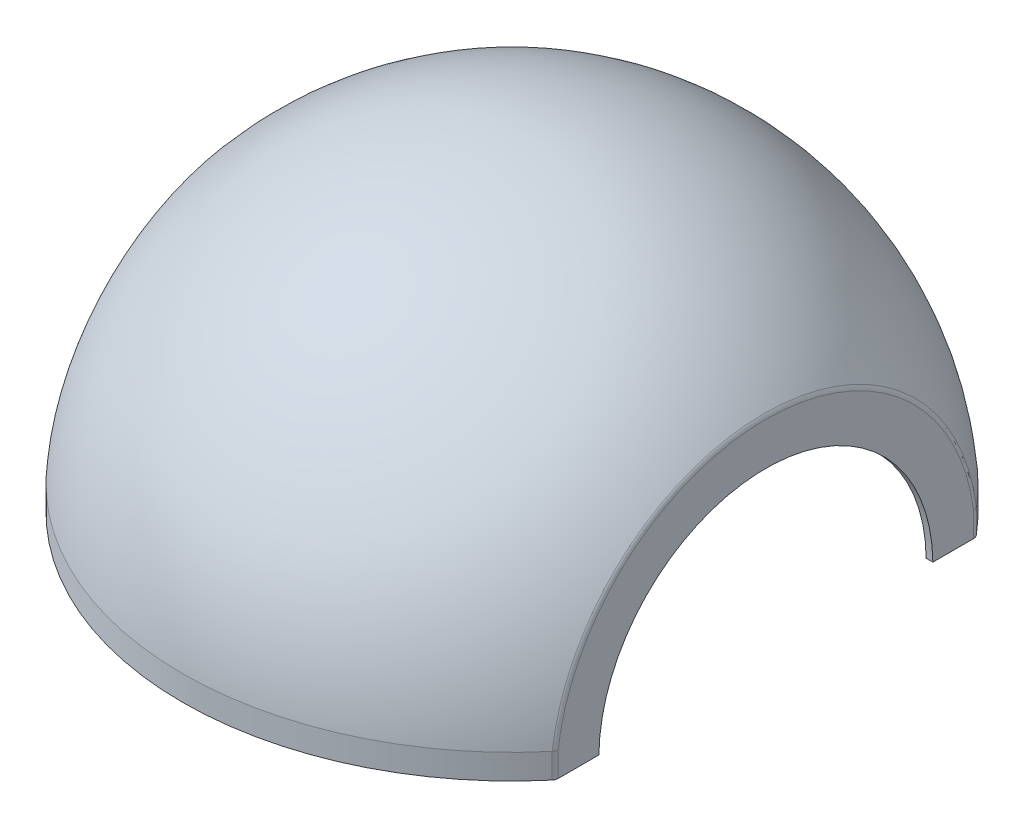
SolidWorks part; units mm, degrees
ref_plane "Face" through (0, 0, 0) normal (0, 0, 1) x (1, 0, 0)
ref_plane "Dessus" through (0, 0, 0) normal (0, 1, 0) x (1, 0, 0)
ref_plane "Droite" through (0, 0, 0) normal (1, 0, 0) x (0, 0, -1)
sketch "Esquisse1" plane through (0, 0, 0) normal (0, 0, 1) x (1, 0, 0)
  line L1 (148, 12.1758) -> (148, 1)
  line L3 (145, 1) -> (145, 12.052)
  line L5 (145, 1) -> (148, 1)
  line L6 (0, 0) -> (0, 184.3027) construction
  line L7 (0, 148.5) -> (0, 145.5)
  arc A0 (145, 12.052) -> (0, 145.5) centre (0, 0) ccw
  arc A1 (148, 12.1758) -> (0, 148.5) centre (0, 0) ccw
  dimension "D1" = 148.5
  dimension "D6" = 145.5
  dimension "D3" = 148
  dimension "D4" = 3
  dimension "D7" = 1
revolve "Révolution4" add sketch "Esquisse1" angle 360 about L6
sketch "Esquisse2" plane through (0, 0, 0) normal (0, 0, 1) x (1, 0, 0)
  line L1 (-114, 150) -> (114, 150)
  line L2 (-114, 150) -> (-114, -5)
  line L3 (-114, -5) -> (114, -5)
  line L4 (114, 150) -> (114, -5)
  dimension "D1" = 114
  dimension "D2" = 114
extrude "Enlèv. mat.-Extru.1" cut sketch "Esquisse2" against normal mid plane 300 flip side to cut
sketch "Esquisse3" plane through (114, 0, 0) normal (1, 0, 0) x (0, 0, -1)
  line L0 (-93.9947, 1) -> (-74.9933, 1)
  line L1 (74.9933, 1) -> (93.9947, 1)
  arc A0 (93.9947, 1) -> (-93.9947, 1) centre (0, 0) ccw
  arc A1 (74.9933, 1) -> (-74.9933, 1) centre (0, 0) ccw
  dimension "D2" = 75
  dimension "D3" = 94
  dimension "D1" = 1
extrude "Boss.-Extru.1" add sketch "Esquisse3" against normal blind 3
sketch "Esquisse4" plane through (-114, 0, 0) normal (-1, 0, 0) x (0, 0, 1)
  line L0 (-93.9947, 1) -> (-74.9933, 1)
  line L1 (74.9933, 1) -> (93.9947, 1)
  arc A0 (93.9947, 1) -> (-93.9947, 1) centre (0, 0) ccw
  arc A1 (74.9933, 1) -> (-74.9933, 1) centre (0, 0) ccw
  dimension "D2" = 75
  dimension "D3" = 94
  dimension "D1" = 1
extrude "Boss.-Extru.2" add sketch "Esquisse4" against normal blind 3
fillet "Congé1" radius 3 6 edges at (-114, 95.1643, 0) (-114, 6.5879, -94.3822) (-114, 6.5879, 94.3822) (114, 95.1643, 0) (114, 6.5879, -94.3822) (114, 6.5879, 94.3822)
